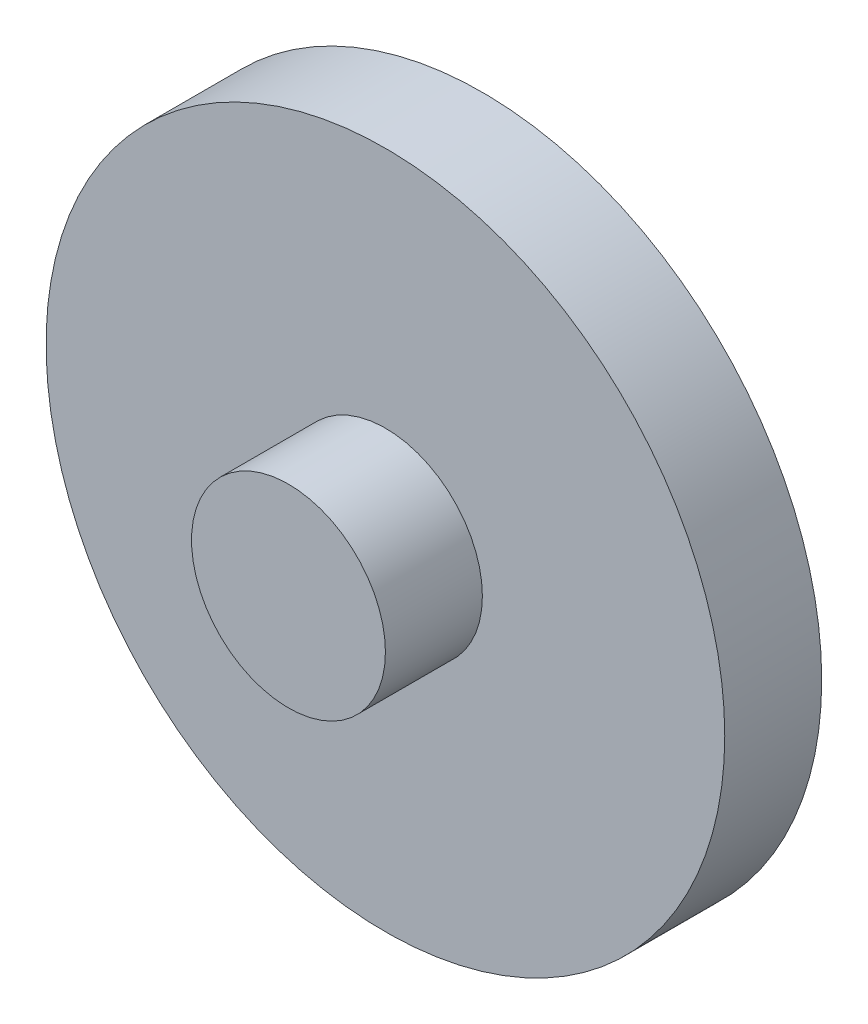
SolidWorks part; units mm, degrees
ref_plane "Front Plane" through (0, 0, 0) normal (0, 0, 1) x (1, 0, 0)
ref_plane "Top Plane" through (0, 0, 0) normal (0, 1, 0) x (1, 0, 0)
ref_plane "Right Plane" through (0, 0, 0) normal (1, 0, 0) x (0, 0, -1)
sketch "Sketch1" plane through (0, 0, 0) normal (0, 0, 1) x (1, 0, 0)
  circle A0 centre (0, 0) radius 17.5
  circle A1 centre (0, 0) radius 5
  dimension "D1" = 35
  dimension "D2" = 10
extrude "Boss-Extrude1" add sketch "Sketch1" along normal blind 5
extrude "Boss-Extrude2" add sketch "Sketch1<2>" along normal blind 10 contours A1
sketch "Sketch1<2>" plane through (0, 0, 0) normal (0, 0, 1) x (1, 0, 0) same geometry as "Sketch1"
